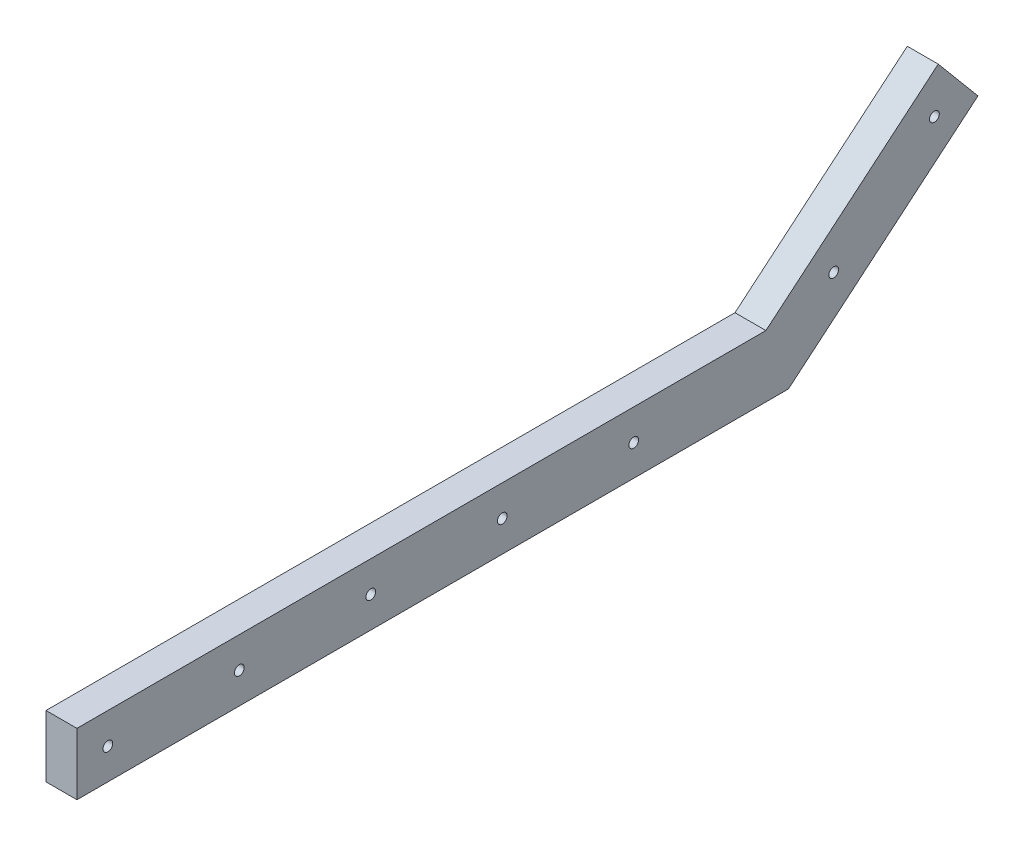
SolidWorks part; units mm, degrees
ref_plane "Front Plane" through (0, 0, 0) normal (0, 0, 1) x (1, 0, 0)
ref_plane "Top Plane" through (0, 0, 0) normal (0, 1, 0) x (1, 0, 0)
ref_plane "Right Plane" through (0, 0, 0) normal (1, 0, 0) x (0, 0, -1)
sketch "Sketch1" plane through (0, 0, 0) normal (1, 0, 0) x (0, 0, -1)
  line L8 (0, 0) -> (-565.7103, 0)
  line L9 (-565.7103, 0) -> (-565.7103, -50.8)
  line L10 (-565.7103, -50.8) -> (18.4897, -50.8)
  line L11 (18.4897, -50.8) -> (174.1499, 79.8144)
  line L12 (0, 0) -> (141.4963, 118.7295)
  line L13 (141.4963, 118.7295) -> (174.1499, 79.8144)
  dimension "D1" = 50.8
  dimension "D2" = 50.8
  dimension "D3" = 584.2
  dimension "D4" = 203.2
  dimension "D5" = 140
extrude "Boss-Extrude1" add sketch "Sketch1" along normal blind 25.4 contours L8 L9 L10 L11 L13 L12
sketch "Sketch2" plane through (0, 0, 0) normal (-1, 0, 0) x (0, 0, 1)
  line L0 (565.7103, -25.4) -> (-95.6238, -25.4) construction
  line L1 (565.7103, 0) -> (565.7103, -50.8) construction
  line L2 (-157.8231, 99.272) -> (76.3227, -97.1997) construction
  line L3 (-141.4963, 118.7295) -> (-174.1499, 79.8144) construction
  circle A0 centre (540.3103, -25.4) radius 4
  circle A1 centre (-138.3656, 82.9452) radius 4
  dimension "D1" = 8
  dimension "D3" = 8
  dimension "D2" = 25.4
  dimension "D4" = 25.4
extrude "Cut-Extrude1" cut sketch "Sketch2" against normal through all
pattern_linear "LPattern1" count 5 spacing 107.95 along (0, 0, -1) of "Cut-Extrude1"
pattern_linear "LPattern2" count 2 spacing 107.95 along (0, -0.6428, 0.766) of face at (25.4, 82.9452, -134.3656)
equation "\"w\"= 2"
equation "\"l2\" = 8"
equation "\"l1\"= 23"
equation "\"D1@Sketch1\"=\"w\""
equation "\"D2@Sketch1\"=\"2\""
equation "\"D3@Sketch1\"=\"l1\""
equation "\"D4@Sketch1\"=\"l2\""
equation "\"a\"= 180 - 40"
equation "\"D5@Sketch1\"=\"a\""
equation "\"D1@LPattern1\"=(\"l1\"/4.25)"
